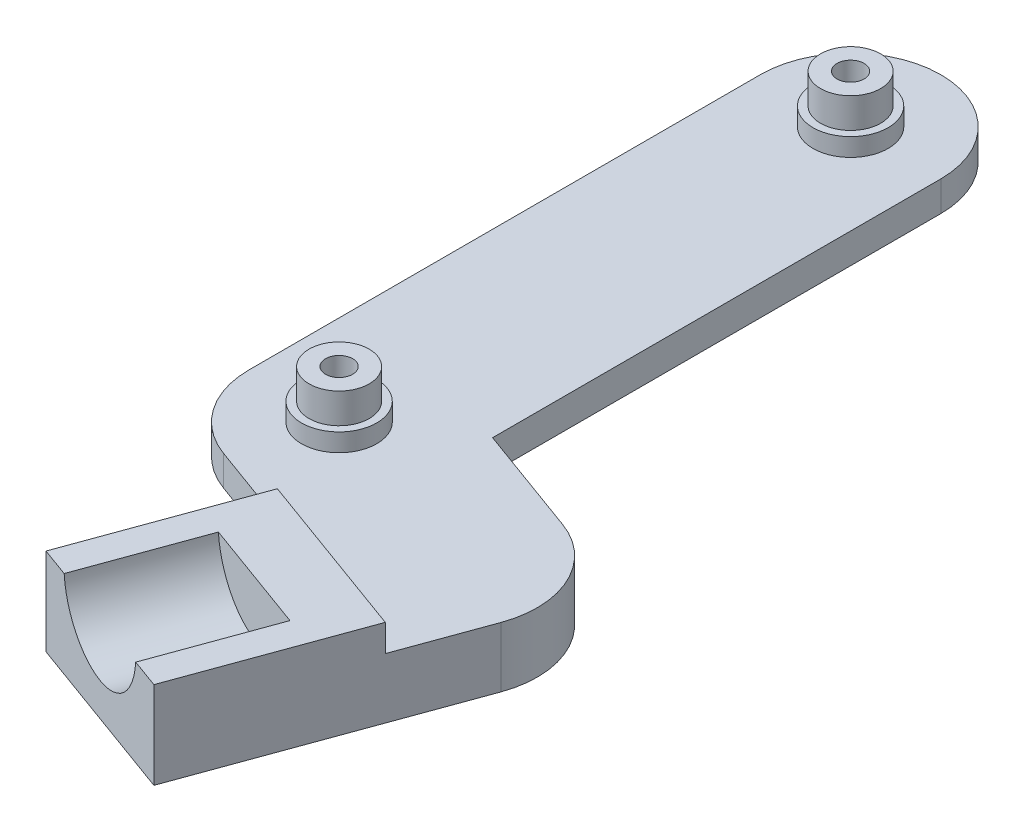
SolidWorks part; units mm, degrees
material "7075-T6 (SN)"
ref_plane "정면" through (0, 0, 0) normal (0, 0, 1) x (1, 0, 0)
ref_plane "윗면" through (0, 0, 0) normal (0, 1, 0) x (1, 0, 0)
ref_plane "우측면" through (0, 0, 0) normal (1, 0, 0) x (0, 0, -1)
sketch "스케치1" plane through (0, 0, 0) normal (0, 1, 0) x (1, 0, 0)
  line L0 (0, 0) -> (0, 85) construction
  line L1 (-15, 0) -> (-15, 85)
  line L2 (15, 0) -> (15, 85)
  arc A0 (-15, 0) -> (15, 0) centre (0, 0) ccw
  arc A1 (15, 85) -> (-15, 85) centre (0, 85) ccw
  point P3 (0, 42.5)
  dimension "D2" = 15
  dimension "D1" = 85
extrude "보스-돌출1" add sketch "스케치1" along normal blind 5 contours A1 L1 A0 L2
sketch "스케치2" plane through (0, 5, 0) normal (0, 1, 0) x (1, 0, 0)
  line L0 (0, 85) -> (0, 0) construction
  circle A0 centre (0, 85) radius 6.25
  circle A1 centre (0, 0) radius 6.25
  dimension "D2" = 12.5
  dimension "D3" = 12.5
  dimension "D1" = 85
extrude "보스-돌출2" add sketch "스케치2" along normal blind 3
sketch "스케치3" plane through (0, 8, 0) normal (0, 1, 0) x (1, 0, 0)
  circle A0 centre (0, 85) radius 5
  circle A1 centre (0, 0) radius 5
  dimension "D1" = 10
  dimension "D2" = 10
extrude "보스-돌출3" add sketch "스케치3" along normal blind 5
sketch "스케치4" plane through (0, 0, 0) normal (0, -1, 0) x (1, 0, 0)
  line L0 (0, -85) -> (0, -20) construction
  dimension "D1" = 65
hole_wizard "M4 남비 머리 나사용 카운터보어1" positions "스케치5" profile "스케치7" counterbore size "M4" standard "ISO" end condition through all
sketch "스케치5" plane through (0, 0, 0) normal (0, -1, 0) x (-1, 0, 0)
  point P3 (0, 85)
  point P10 (0, 0)
  dimension "D1" = 85
sketch "스케치7" plane through (0, 0, -85) normal (1, 0, 0) x (0, 0, -1)
  line L0 (0, 0) -> (0, 13)
  line L1 (0, 13) -> (2.25, 13)
  line L3 (2.25, 13) -> (2.25, 4)
  line L4 (2.25, 4) -> (4.5, 4)
  line L5 (4.5, 4) -> (4.5, 0)
  line L7 (4.5, 0) -> (0, 0)
  line L11 (0, -6.35) -> (0, 107.95) construction
  dimension "관통 구멍 지름" = 4.5
  dimension "관통 구멍 깊이" = 13
  dimension "카운터보어 지름" = 9
  dimension "카운터보어 깊이" = 4
sketch "스케치8" plane through (0, 0, 0) normal (0, -1, 0) x (1, 0, 0)
  line L0 (0, 0) -> (28.1908, 10.2606) construction
  line L1 (15, 0) -> (15, -85) construction
  line L2 (0, 0) -> (28.1908, 10.2606) construction
  line L3 (-5.1303, 14.0954) -> (23.0605, 24.356)
  line L4 (15, -10.5031) -> (33.3211, -3.8348)
  line L5 (15, 0) -> (15, -10.5031)
  arc A1 (33.3211, -3.8348) -> (23.0605, 24.356) centre (28.1908, 10.2606) ccw
  arc A2 (15, 0) -> (-15, 0) centre (0, 0) ccw construction
  arc A3 (15, 0) -> (-5.1303, 14.0954) centre (0, 0) ccw
  point P3 (15, 5.4596)
  dimension "D3" = 15
  dimension "D1" = 110
  dimension "D2" = 30
extrude "보스-돌출4" add sketch "스케치8" against normal blind 5
sketch "스케치9" plane through (0, 0, 0) normal (0, -1, 0) x (1, 0, 0)
  line L0 (28.1908, 10.2606) -> (17.9302, 38.4514) construction
  line L1 (23.0605, 24.356) -> (-5.1303, 14.0954) construction
  line L2 (28.1908, 10.2606) -> (17.9302, 38.4514) construction
  line L3 (14.0954, 5.1303) -> (3.8348, 33.3211)
  line L4 (42.2862, 15.3909) -> (32.0256, 43.5817)
  line L5 (3.8348, 33.3211) -> (-1.2955, 47.4165)
  line L6 (32.0256, 43.5817) -> (26.8953, 57.6771)
  line L7 (-1.2955, 47.4165) -> (26.8953, 57.6771)
  arc A0 (14.0954, 5.1303) -> (42.2862, 15.3909) centre (28.1908, 10.2606) ccw
  point P5 (23.0605, 24.356)
  dimension "D3" = 15
  dimension "D5" = 30
  dimension "D1" = 30
  dimension "D2" = 90
  dimension "D4" = 45
  dimension "D6" = 30
extrude "보스-돌출5" add sketch "스케치9" against normal blind 5 and the other way blind 5
sketch "스케치13" plane through (0, 5, 0) normal (0, 1, 0) x (1, 0, 0)
  line L0 (42.2862, -15.3909) -> (26.8953, -57.6771) construction
  line L1 (-1.2955, -47.4165) -> (8.9651, -19.2257) construction
  line L2 (26.8953, -57.6771) -> (-1.2955, -47.4165) construction
  line L3 (37.1559, -29.4863) -> (26.8953, -57.6771)
  line L4 (-1.2955, -47.4165) -> (8.9651, -19.2257)
  line L5 (26.8953, -57.6771) -> (-1.2955, -47.4165)
  line L6 (8.9651, -19.2257) -> (37.1559, -29.4863)
extrude "보스-돌출6" add sketch "스케치13" along normal blind 4.5
sketch "스케치15" plane through (-15.3909, 0, 42.2862) normal (-0.342, 0, 0.9397) x (0.9397, 0, 0.342)
  line L0 (15, 9.5) -> (45, 9.5) construction
  line L1 (14.3731, 10.5) -> (45.6844, 10.5) construction
  line L2 (45, -5) -> (45, 9.5) construction
  circle A0 centre (30, 10.5) radius 10
  point P6 (0, 0)
  point P9 (0, 0)
  dimension "D1" = 20
  dimension "D2" = 1
  dimension "D3" = 15
extrude "컷-돌출2" cut sketch "스케치15" against normal blind 20
